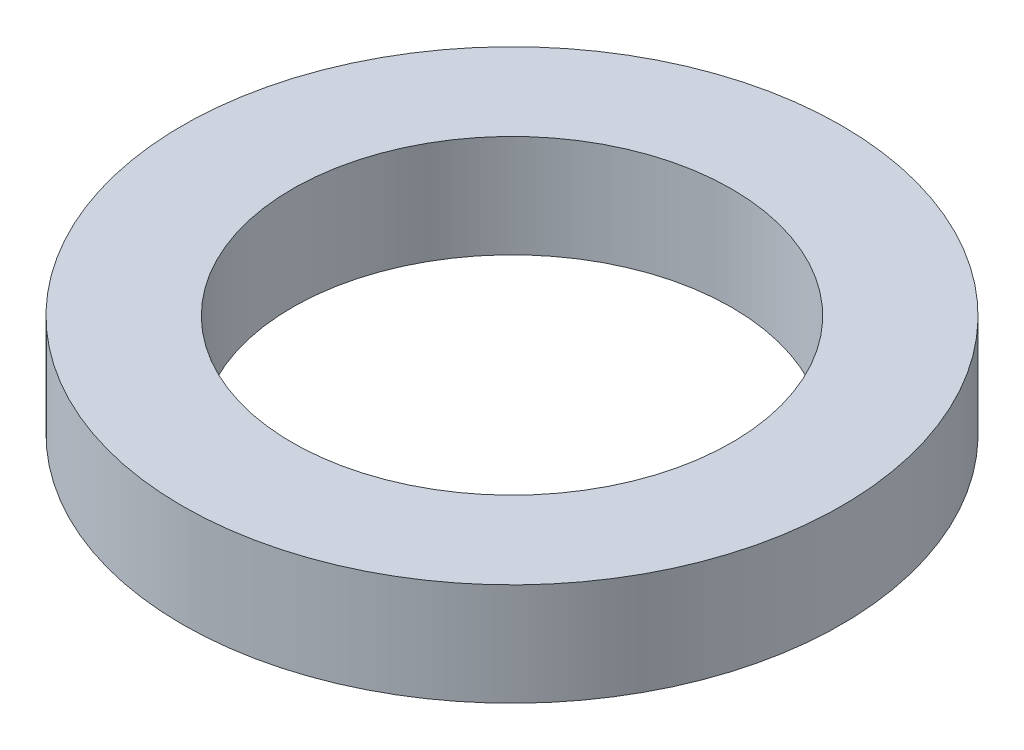
SolidWorks part; units mm, degrees
ref_plane "Front Plane" through (0, 0, 0) normal (0, 0, 1) x (1, 0, 0)
ref_plane "Top Plane" through (0, 0, 0) normal (0, 1, 0) x (1, 0, 0)
ref_plane "Right Plane" through (0, 0, 0) normal (1, 0, 0) x (0, 0, -1)
sketch "Sketch1" plane through (0, 0, 0) normal (0, 1, 0) x (1, 0, 0)
  circle A0 centre (0, 0) radius 67.5
  dimension "FLANGE_OD" = 135
extrude "Boss-Extrude1" add sketch "Sketch1" along normal blind 21
sketch "Sketch2" plane through (0, 0, 0) normal (0, 1, 0) x (1, 0, 0)
  circle A0 centre (0, 0) radius 45
  dimension "BORE_D" = 90
extrude "Cut-Extrude1" cut sketch "Sketch2" along normal through all
sketch "Sketch3" plane through (0, 21, 0) normal (0, 1, 0) x (1, 0, 0)
  circle A0 centre (0, 0) radius 29.0182 construction
  circle A1 centre (-29.0182, 0) radius 2.4362
  dimension "BOLT_D" = 4.8724
  dimension "BOLT_PCD" = 58.0364
extrude "Cut-Extrude2" cut sketch "Sketch3" against normal blind 20.7334 rebuild error yes
pattern_circular "CirPattern1" count 5 over 360 rebuild error yes
